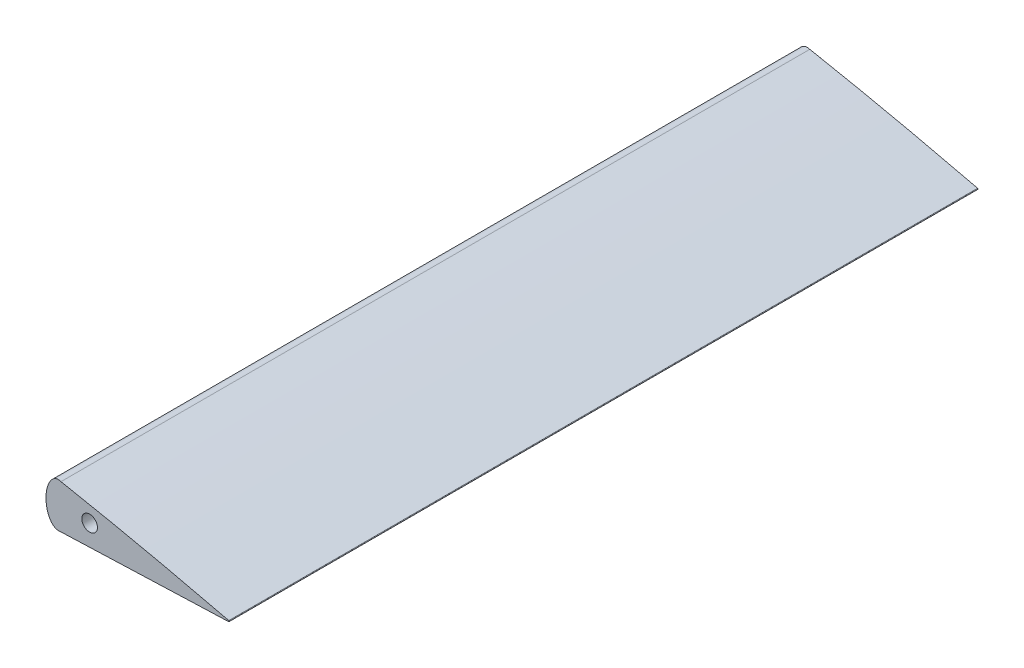
SolidWorks part; units mm, degrees
ref_plane "Front Plane" through (0, 0, 0) normal (0, 0, 1) x (1, 0, 0)
ref_plane "Top Plane" through (0, 0, 0) normal (0, 1, 0) x (1, 0, 0)
ref_plane "Right Plane" through (0, 0, 0) normal (1, 0, 0) x (0, 0, -1)
curve "Curve1"
  spline degree 3 poles (164, 0.0982, 0) (163.4533, 0.2279, 0) (162.3601, 0.4871, 0) (160.7202, 0.8748, 0) (159.0803, 1.2611, 0) (156.8943, 1.7719, 0) (154.162, 2.401, 0) (150.8818, 3.1375, 0) (147.6017, 3.8566, 0) (144.3217, 4.5599, 0) (141.0417, 5.2462, 0) (137.7618, 5.9156, 0) (134.4817, 6.5665, 0) (131.2018, 7.1999, 0) (127.9217, 7.8138, 0) (124.6417, 8.4092, 0) (121.3616, 8.9846, 0) (118.0816, 9.5413, 0) (114.8016, 10.0781, 0) (111.5216, 10.595, 0) (108.2417, 11.091, 0) (104.9617, 11.5629, 0) (101.6818, 12.0102, 0) (98.4017, 12.4297, 0) (95.1217, 12.8205, 0) (91.8415, 13.1818, 0) (88.5614, 13.5136, 0) (85.2813, 13.8159, 0) (82.0012, 14.0887, 0) (78.7211, 14.3317, 0) (75.441, 14.5432, 0) (72.1609, 14.7199, 0) (68.8807, 14.8594, 0) (65.6005, 14.9592, 0) (62.3202, 15.0161, 0) (59.04, 15.033, 0) (55.7598, 15.0128, 0) (52.4797, 14.9596, 0) (49.1996, 14.8756, 0) (45.9192, 14.7668, 0) (42.6385, 14.6188, 0) (39.3574, 14.416, 0) (36.0758, 14.1416, 0) (32.7935, 13.7797, 0) (29.5117, 13.3118, 0) (26.2304, 12.7369, 0) (22.9482, 12.0591, 0) (19.664, 11.2714, 0) (16.3781, 10.3517, 0) (13.0927, 9.2716, 0) (10.3582, 8.2399, 0) (8.1787, 7.2692, 0) (6.5271, 6.4236, 0) (4.8606, 5.419, 0) (3.3222, 4.2467, 0) (2.1668, 3.1342, 0) (1.2848, 2.24, 0) (0.7248, 1.5863, 0) (0.3565, 1.0237, 0) (0.1763, 0.6552, 0) (0.0613, 0.3376, 0) (-0.0429, -0.1211, 0) (0.0101, -0.5985, 0) (0.1762, -1.0141, 0) (0.3547, -1.3445, 0) (0.7171, -1.8262, 0) (1.2698, -2.3368, 0) (2.1318, -2.9202, 0) (3.3549, -3.3928, 0) (4.9153, -3.7072, 0) (6.5542, -4.033, 0) (8.1953, -4.2835, 0) (10.3823, -4.5154, 0) (13.1186, -4.6727, 0) (16.3989, -4.8285, 0) (19.6795, -4.9221, 0) (22.9598, -4.9665, 0) (26.2401, -4.9679, 0) (29.5202, -4.9328, 0) (32.8003, -4.8689, 0) (36.0803, -4.7827, 0) (39.3602, -4.679, 0) (42.6401, -4.563, 0) (45.9201, -4.4399, 0) (49.2, -4.3141, 0) (52.48, -4.1907, 0) (55.76, -4.07, 0) (59.04, -3.9501, 0) (62.32, -3.8313, 0) (65.6, -3.7121, 0) (68.88, -3.5923, 0) (72.16, -3.4722, 0) (75.44, -3.3513, 0) (78.72, -3.2307, 0) (82, -3.1097, 0) (85.28, -2.989, 0) (88.56, -2.8685, 0) (91.84, -2.7482, 0) (95.12, -2.6278, 0) (98.4, -2.5074, 0) (101.68, -2.387, 0) (104.96, -2.2667, 0) (108.24, -2.1461, 0) (111.52, -2.0255, 0) (114.8, -1.9053, 0) (118.08, -1.7846, 0) (121.36, -1.6644, 0) (124.64, -1.5437, 0) (127.92, -1.4234, 0) (131.2, -1.3027, 0) (134.48, -1.1825, 0) (137.76, -1.0618, 0) (141.04, -0.9416, 0) (144.32, -0.8209, 0) (147.6, -0.7007, 0) (150.88, -0.58, 0) (154.16, -0.4598, 0) (156.8933, -0.3592, 0) (159.08, -0.279, 0) (160.72, -0.2188, 0) (162.36, -0.1586, 0) (163.4533, -0.1184, 0) (164, -0.0982, 0) knots 0 0 0 0 0.005028 0.010055 0.015081 0.020105 0.030145 0.040174 0.050191 0.060198 0.070194 0.08018 0.090156 0.100121 0.110076 0.12002 0.129954 0.139879 0.149793 0.159699 0.169594 0.17948 0.189355 0.199219 0.209073 0.218917 0.228751 0.238577 0.248396 0.258207 0.268012 0.277811 0.287604 0.297393 0.307179 0.316964 0.326749 0.336535 0.346322 0.356113 0.365908 0.375711 0.385531 0.395376 0.405259 0.415192 0.425184 0.435248 0.445412 0.455711 0.466191 0.471552 0.477055 0.482787 0.488946 0.494316 0.497126 0.500187 0.502001 0.503128 0.50385 0.50502 0.507318 0.507987 0.509024 0.510668 0.513358 0.515716 0.519949 0.524973 0.529954 0.534903 0.539824 0.54963 0.559425 0.569214 0.579 0.588784 0.59857 0.608356 0.618144 0.627933 0.637724 0.647515 0.657307 0.667099 0.67689 0.686681 0.696472 0.706263 0.716054 0.725846 0.735637 0.745428 0.755219 0.765011 0.774802 0.784593 0.794384 0.804176 0.813967 0.823758 0.833549 0.84334 0.853132 0.862923 0.872714 0.882505 0.892297 0.902088 0.911879 0.92167 0.931461 0.941253 0.951044 0.960835 0.970626 0.980418 0.985313 0.990209 0.995104 1 1 1 1
sketch "Sketch2" plane through (0, 0, 0) normal (0, 0, 1) x (1, 0, 0)
  line L0 (0, 0) -> (164.0777, 0) construction
  arc A0 (164, 0.0982) -> (164, -0.0982) centre (163.9767, 0) cw
  spline S0 degree 3 poles (2058.1801, 5665.0083) (508.1071, -100.6508) (336.8613, -40.7697) (160.7202, 0.8748) (159.0803, 1.2611) (156.8943, 1.7719) (154.162, 2.401) (150.8818, 3.1375) (147.6017, 3.8566) (144.3217, 4.5599) (141.0417, 5.2462) (137.7618, 5.9156) (134.4817, 6.5665) (131.2018, 7.1999) (127.9217, 7.8138) (124.6417, 8.4092) (121.3616, 8.9846) (118.0816, 9.5413) (114.8016, 10.0781) (111.5216, 10.595) (108.2417, 11.091) (104.9617, 11.5629) (101.6818, 12.0102) (98.4017, 12.4297) (95.1217, 12.8205) (91.8415, 13.1818) (88.5614, 13.5136) (85.2813, 13.8159) (82.0012, 14.0887) (78.7211, 14.3317) (75.441, 14.5432) (72.1609, 14.7199) (68.8807, 14.8594) (65.6005, 14.9592) (62.3202, 15.0161) (59.04, 15.033) (55.7598, 15.0128) (52.4797, 14.9596) (49.1996, 14.8756) (45.9192, 14.7668) (42.6385, 14.6188) (39.3574, 14.416) (36.0758, 14.1416) (32.7935, 13.7797) (29.5117, 13.3118) (26.2304, 12.7369) (22.9482, 12.0591) (19.664, 11.2714) (16.3781, 10.3517) (13.0927, 9.2716) (10.3582, 8.2399) (8.1787, 7.2692) (6.5271, 6.4236) (4.8606, 5.419) (3.3222, 4.2467) (2.1668, 3.1342) (1.2848, 2.24) (0.7248, 1.5863) (0.3565, 1.0237) (0.1763, 0.6552) (0.0613, 0.3376) (-0.0429, -0.1211) (0.0101, -0.5985) (0.1762, -1.0141) (0.3547, -1.3445) (0.7171, -1.8262) (1.2698, -2.3368) (2.1318, -2.9202) (3.3549, -3.3928) (4.9153, -3.7072) (6.5542, -4.033) (8.1953, -4.2835) (10.3823, -4.5154) (13.1186, -4.6727) (16.3989, -4.8285) (19.6795, -4.9221) (22.9598, -4.9665) (26.2401, -4.9679) (29.5202, -4.9328) (32.8003, -4.8689) (36.0803, -4.7827) (39.3602, -4.679) (42.6401, -4.563) (45.9201, -4.4399) (49.2, -4.3141) (52.48, -4.1907) (55.76, -4.07) (59.04, -3.9501) (62.32, -3.8313) (65.6, -3.7121) (68.88, -3.5923) (72.16, -3.4722) (75.44, -3.3513) (78.72, -3.2307) (82, -3.1097) (85.28, -2.989) (88.56, -2.8685) (91.84, -2.7482) (95.12, -2.6278) (98.4, -2.5074) (101.68, -2.387) (104.96, -2.2667) (108.24, -2.1461) (111.52, -2.0255) (114.8, -1.9053) (118.08, -1.7846) (121.36, -1.6644) (124.64, -1.5437) (127.92, -1.4234) (131.2, -1.3027) (134.48, -1.1825) (137.76, -1.0618) (141.04, -0.9416) (144.32, -0.8209) (147.6, -0.7007) (150.88, -0.58) (154.16, -0.4598) (156.8933, -0.3592) (159.08, -0.279) (160.72, -0.2188) (441.1862, 10.0645) (720.6791, 31.9333) (1216.3131, -5842.5162) knots -1.604726 -1.604726 -1.604726 -1.604726 0.005028 0.010055 0.015081 0.020105 0.030145 0.040174 0.050191 0.060198 0.070194 0.08018 0.090156 0.100121 0.110076 0.12002 0.129954 0.139879 0.149793 0.159699 0.169594 0.17948 0.189355 0.199219 0.209073 0.218917 0.228751 0.238577 0.248396 0.258207 0.268012 0.277811 0.287604 0.297393 0.307179 0.316964 0.326749 0.336535 0.346322 0.356113 0.365908 0.375711 0.385531 0.395376 0.405259 0.415192 0.425184 0.435248 0.445412 0.455711 0.466191 0.471552 0.477055 0.482787 0.488946 0.494316 0.497126 0.500187 0.502001 0.503128 0.50385 0.50502 0.507318 0.507987 0.509024 0.510668 0.513358 0.515716 0.519949 0.524973 0.529954 0.534903 0.539824 0.54963 0.559425 0.569214 0.579 0.588784 0.59857 0.608356 0.618144 0.627933 0.637724 0.647515 0.657307 0.667099 0.67689 0.686681 0.696472 0.706263 0.716054 0.725846 0.735637 0.745428 0.755219 0.765011 0.774802 0.784593 0.794384 0.804176 0.813967 0.823758 0.833549 0.84334 0.853132 0.862923 0.872714 0.882505 0.892297 0.902088 0.911879 0.92167 0.931461 0.941253 0.951044 0.960835 0.970626 0.980418 0.985313 0.990209 0.995104 3.496991 3.496991 3.496991 3.496991 only from (164, 0.0982) to (164, -0.0982) construction
  spline S1 degree 3 poles (164, 0.0982) (163.4533, 0.2279) (162.3601, 0.4871) (160.7202, 0.8748) (159.0803, 1.2611) (156.8943, 1.7719) (154.162, 2.401) (150.8818, 3.1375) (147.6017, 3.8566) (144.3217, 4.5599) (141.0417, 5.2462) (137.7618, 5.9156) (134.4817, 6.5665) (131.2018, 7.1999) (127.9217, 7.8138) (124.6417, 8.4092) (121.3616, 8.9846) (118.0816, 9.5413) (114.8016, 10.0781) (111.5216, 10.595) (108.2417, 11.091) (104.9617, 11.5629) (101.6818, 12.0102) (98.4017, 12.4297) (95.1217, 12.8205) (91.8415, 13.1818) (88.5614, 13.5136) (85.2813, 13.8159) (82.0012, 14.0887) (78.7211, 14.3317) (75.441, 14.5432) (72.1609, 14.7199) (68.8807, 14.8594) (65.6005, 14.9592) (62.3202, 15.0161) (59.04, 15.033) (55.7598, 15.0128) (52.4797, 14.9596) (49.1996, 14.8756) (45.9192, 14.7668) (42.6385, 14.6188) (39.3574, 14.416) (36.0758, 14.1416) (32.7935, 13.7797) (29.5117, 13.3118) (26.2304, 12.7369) (22.9482, 12.0591) (19.664, 11.2714) (16.3781, 10.3517) (13.0927, 9.2716) (10.3582, 8.2399) (8.1787, 7.2692) (6.5271, 6.4236) (4.8606, 5.419) (3.3222, 4.2467) (2.1668, 3.1342) (1.2848, 2.24) (0.7248, 1.5863) (0.3565, 1.0237) (0.1763, 0.6552) (0.0613, 0.3376) (-0.0429, -0.1211) (0.0101, -0.5985) (0.1762, -1.0141) (0.3547, -1.3445) (0.7171, -1.8262) (1.2698, -2.3368) (2.1318, -2.9202) (3.3549, -3.3928) (4.9153, -3.7072) (6.5542, -4.033) (8.1953, -4.2835) (10.3823, -4.5154) (13.1186, -4.6727) (16.3989, -4.8285) (19.6795, -4.9221) (22.9598, -4.9665) (26.2401, -4.9679) (29.5202, -4.9328) (32.8003, -4.8689) (36.0803, -4.7827) (39.3602, -4.679) (42.6401, -4.563) (45.9201, -4.4399) (49.2, -4.3141) (52.48, -4.1907) (55.76, -4.07) (59.04, -3.9501) (62.32, -3.8313) (65.6, -3.7121) (68.88, -3.5923) (72.16, -3.4722) (75.44, -3.3513) (78.72, -3.2307) (82, -3.1097) (85.28, -2.989) (88.56, -2.8685) (91.84, -2.7482) (95.12, -2.6278) (98.4, -2.5074) (101.68, -2.387) (104.96, -2.2667) (108.24, -2.1461) (111.52, -2.0255) (114.8, -1.9053) (118.08, -1.7846) (121.36, -1.6644) (124.64, -1.5437) (127.92, -1.4234) (131.2, -1.3027) (134.48, -1.1825) (137.76, -1.0618) (141.04, -0.9416) (144.32, -0.8209) (147.6, -0.7007) (150.88, -0.58) (154.16, -0.4598) (156.8933, -0.3592) (159.08, -0.279) (160.72, -0.2188) (162.36, -0.1586) (163.4533, -0.1184) (164, -0.0982) knots 0 0 0 0 0.005028 0.010055 0.015081 0.020105 0.030145 0.040174 0.050191 0.060198 0.070194 0.08018 0.090156 0.100121 0.110076 0.12002 0.129954 0.139879 0.149793 0.159699 0.169594 0.17948 0.189355 0.199219 0.209073 0.218917 0.228751 0.238577 0.248396 0.258207 0.268012 0.277811 0.287604 0.297393 0.307179 0.316964 0.326749 0.336535 0.346322 0.356113 0.365908 0.375711 0.385531 0.395376 0.405259 0.415192 0.425184 0.435248 0.445412 0.455711 0.466191 0.471552 0.477055 0.482787 0.488946 0.494316 0.497126 0.500187 0.502001 0.503128 0.50385 0.50502 0.507318 0.507987 0.509024 0.510668 0.513358 0.515716 0.519949 0.524973 0.529954 0.534903 0.539824 0.54963 0.559425 0.569214 0.579 0.588784 0.59857 0.608356 0.618144 0.627933 0.637724 0.647515 0.657307 0.667099 0.67689 0.686681 0.696472 0.706263 0.716054 0.725846 0.735637 0.745428 0.755219 0.765011 0.774802 0.784593 0.794384 0.804176 0.813967 0.823758 0.833549 0.84334 0.853132 0.862923 0.872714 0.882505 0.892297 0.902088 0.911879 0.92167 0.931461 0.941253 0.951044 0.960835 0.970626 0.980418 0.985313 0.990209 0.995104 1 1 1 1
extrude "Boss-Extrude1" add sketch "Sketch2" along normal blind 1246.6
sketch "Sketch3" plane through (0, 0, 1246.6) normal (0, 0, 1) x (1, 0, 0)
  line L0 (0, 0) -> (164.0777, 0) construction
  line L2 (-0.0541, 26.1225) -> (131.2777, 26.1225)
  line L3 (-0.0541, 26.1225) -> (-0.0541, -6.5054)
  line L4 (-0.0541, -6.5054) -> (131.2777, -6.5054)
  line L5 (131.2777, 26.1225) -> (131.2777, -6.5054)
  arc A0 (164, -0.0982) -> (164, 0.0982) centre (163.9767, 0) ccw construction
  dimension "D1" = 32.8
extrude "Aileron chord" cut sketch "Sketch3" against normal blind 1246.6
sketch "Sketch4" plane through (0, 0, 0) normal (0, 1, 0) x (1, 0, 0)
  line L0 (164, 0) -> (131.2777, 0) construction
  line L1 (60.8267, -143.8) -> (231.8967, -143.8)
  line L2 (60.8267, -143.8) -> (60.8267, -1254.4391)
  line L3 (60.8267, -1254.4391) -> (231.8967, -1254.4391)
  line L4 (231.8967, -143.8) -> (231.8967, -1254.4391)
  dimension "D1" = 143.8
extrude "Aileron span " cut sketch "Sketch4" against normal blind 10 and the other way blind 10
sketch "Sketch5" plane through (0, 0, 0) normal (0, 0, -1) x (-1, 0, 0)
  line L0 (-131.2777, 2.9411) -> (-146.661, 2.9411) construction
  line L1 (-131.2777, 7.1822) -> (-131.2777, -1.3) construction
  circle A0 centre (-137.2777, 2.9411) radius 1.5
  dimension "D1" = 3
  dimension "D2" = 6
extrude "Aileron spar hole" cut sketch "Sketch5" against normal through all
sketch "Sketch6" plane through (0, 0, 0) normal (0, 0, -1) x (-1, 0, 0)
  line L0 (-131.2777, 7.1822) -> (-131.2777, -1.3) construction
  ellipse E0 centre (-131.2777, 2.9411) end of major axis (-131.2777, 7.1822) minor radius 2.3804
extrude "Aileron leading edge" add sketch "Sketch6" against normal blind 143.8
